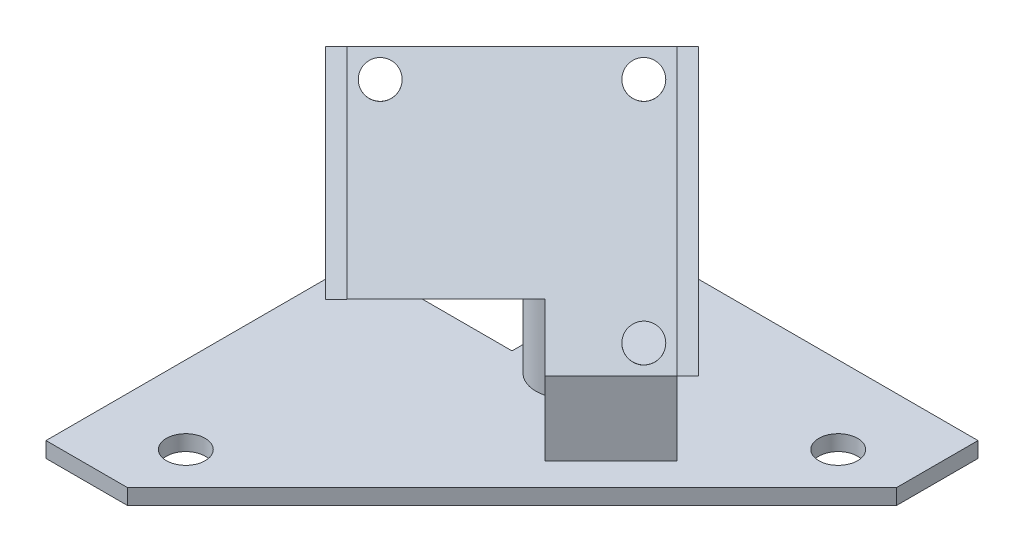
SolidWorks part; units mm, degrees
ref_plane "Front" through (0, 0, 0) normal (0, 0, 1) x (1, 0, 0)
ref_plane "Top" through (0, 0, 0) normal (0, 1, 0) x (1, 0, 0)
ref_plane "Right" through (0, 0, 0) normal (1, 0, 0) x (0, 0, -1)
sketch "草图1" plane through (0, 0, 0) normal (0, 1, 0) x (1, 0, 0)
  line L0 (87.1745, 16.672) -> (1.4976, -69.0049)
  line L1 (0, 0) -> (60, 0)
  line L2 (0, 0) -> (0, -60)
  line L3 (0, -60) -> (60, -60)
  line L4 (60, 0) -> (60, -60)
  line L5 (0, 0) -> (20, 0)
  line L6 (0, 0) -> (0, -20)
  line L7 (0, -20) -> (20, -20)
  line L8 (20, 0) -> (20, -20)
  circle A0 centre (10, -52) radius 2.5
  circle A1 centre (52, -10) radius 2.5
  dimension "D5" = 5
  dimension "D8" = 5
  dimension "D1" = 60
  dimension "D2" = 60
  dimension "D3" = 20
  dimension "D4" = 20
  dimension "D6" = 10
  dimension "D7" = 8
  dimension "D9" = 10
  dimension "D10" = 8
  dimension "D11" = 35
extrude "凸台-拉伸1" add sketch "草图1" along normal blind 2 contours L1 L8 L7 L2 L3 L4 region at (25.5687, 0, 25.5687)
ref_plane "基准面1" through (24.3184, 24.0811, 24.3184) normal (0.5792, 0.5736, 0.5792) x (-0.7071, 0, 0.7071)
sketch "草图2" plane through (24.3184, 24.0811, 24.3184) normal (0.5792, 0.5736, 0.5792) x (-0.7071, 0, 0.7071)
  line L0 (20.7547, -10.214) -> (-21.3736, -10.214) construction
  line L1 (-15, 16.786) -> (15, 16.786)
  line L2 (-15, 16.786) -> (-15, -13.214)
  line L3 (-15, -13.214) -> (15, -13.214)
  line L4 (15, 16.786) -> (15, -13.214)
  line L5 (-15, 16.786) -> (15, -13.214) construction
  line L6 (-15, -13.214) -> (15, 16.786) construction
  line L7 (0, -2.8326) -> (0, 36.0846) construction
  line L8 (27.4605, 1.786) -> (-33.4746, 1.786) construction
  line L10 (15, 16.786) -> (-3, 16.786)
  line L11 (15, 16.786) -> (15, 9.786)
  line L12 (15, 9.786) -> (-3, 9.786)
  line L13 (-3, 16.786) -> (-3, 9.786)
  circle A0 centre (12, -10.214) radius 2
  circle A1 centre (-12, -10.214) radius 2
  circle A2 centre (-12, 13.786) radius 2
  circle A3 centre (12, 13.786) radius 2
  point P0 (0, 1.786)
  dimension "D4" = 4
  dimension "D1" = 30
  dimension "D2" = 30
  dimension "D3" = 12
  dimension "D5" = 12
  dimension "D6" = 7
  dimension "D7" = 18
extrude "凸台-拉伸3" add sketch "草图2" along normal blind 2 separate body contours L13 L1 L2 L3 L4 L12 A2 A0 A1 region at (24.9089, 24.0624, 23.7465)
sketch "草图4" plane through (0, 2, 0) normal (0, 1, 0) x (1, 0, 0)
  line L12 (30.4088, -40.3082) -> (33.2478, -43.1473)
  line L13 (17.6808, -53.0362) -> (30.4088, -40.3082)
  line L14 (-5.7896, -29.5657) -> (17.6808, -53.0362)
  line L15 (29.5657, 5.7896) -> (-5.7896, -29.5657)
  line L16 (55.8752, -20.5199) -> (29.5657, 5.7896)
  line L17 (33.2478, -43.1473) -> (55.8752, -20.5199)
  line L18 (30.4088, -40.3082) -> (33.2478, -43.1473)
  line L19 (17.6808, -53.0362) -> (30.4088, -40.3082)
  line L20 (-5.7896, -29.5657) -> (17.6808, -53.0362)
  line L21 (29.5657, 5.7896) -> (-5.7896, -29.5657)
  line L22 (55.8752, -20.5199) -> (29.5657, 5.7896)
  line L23 (33.2478, -43.1473) -> (55.8752, -20.5199)
  circle A0 centre (26.0302, -18.9591) radius 4
  dimension "D2" = 8
  dimension "D3" = 15
  dimension "D4" = 20
  dimension "D1" = 10
extrude "凸台-拉伸4" add sketch "草图4" along normal up to surface (21.7252 mm away) contours A0 region at (26.0302, 2, 18.9591) up to face at (39.8092, 12.7883, 20.0103)
sketch "草图5" plane through (0, 2, 0) normal (0, 1, 0) x (1, 0, 0)
  line L4 (41.7331, -20.5199) -> (33.2478, -29.0052)
  line L5 (42.8915, -21.6783) -> (41.7331, -20.5199)
  line L6 (34.4063, -30.1636) -> (42.8915, -21.6783)
  line L7 (60, 0) -> (20, 0)
  line L8 (20, 0) -> (20, -20)
  line L9 (20, -20) -> (0, -20)
  line L10 (0, -20) -> (0, -60)
  line L11 (0, -60) -> (10.5025, -60)
  line L12 (10.5025, -60) -> (60, -10.5025)
  line L13 (60, -10.5025) -> (60, 0)
  line L14 (60, 0) -> (20, 0)
  line L15 (20, 0) -> (20, -20)
  line L16 (20, -20) -> (0, -20)
  line L17 (0, -20) -> (0, -60)
  line L18 (0, -60) -> (10.5025, -60)
  line L19 (10.5025, -60) -> (60, -10.5025)
  line L20 (60, -10.5025) -> (60, 0)
  line L21 (33.2478, -29.0052) -> (34.4063, -30.1636)
  line L22 (41.7331, -20.5199) -> (33.2478, -29.0052)
  line L23 (42.8915, -21.6783) -> (41.7331, -20.5199)
  line L24 (34.4063, -30.1636) -> (42.8915, -21.6783)
  line L25 (33.2478, -29.0052) -> (34.4063, -30.1636)
  dimension "D1" = 0
  dimension "D2" = 0
extrude "凸台-拉伸5" add sketch "草图5" along normal up to next contours L22 L25 L24 L23 region at (38.0697, 2, 25.3418)
sketch "草图6" plane through (25.4769, 25.2283, 25.4769) normal (0.5792, 0.5736, 0.5792) x (0.4511, 0.3663, -0.8138)
  line L0 (-7.5069, 18.5271) -> (-17.7929, -2.0447)
  line L1 (-7.5069, 18.5271) -> (-9.2958, 19.4216)
  line L2 (-17.7929, -2.0447) -> (-19.5817, -1.1503)
  line L3 (-9.2958, 19.4216) -> (-19.5817, -1.1503)
  line L4 (19.3259, 5.1107) -> (5.9095, -21.7221)
  line L5 (19.3259, 5.1107) -> (21.1147, 4.2163)
  line L6 (5.9095, -21.7221) -> (7.6983, -22.6165)
  line L7 (21.1147, 4.2163) -> (7.6983, -22.6165)
  dimension "D1" = 2
  dimension "D2" = 2
extrude "凸台-拉伸6" add sketch "草图6" against normal up to surface (2 mm away) and the other way blind 3 up to face at (28.8586, 22.0521, 21.7875)
